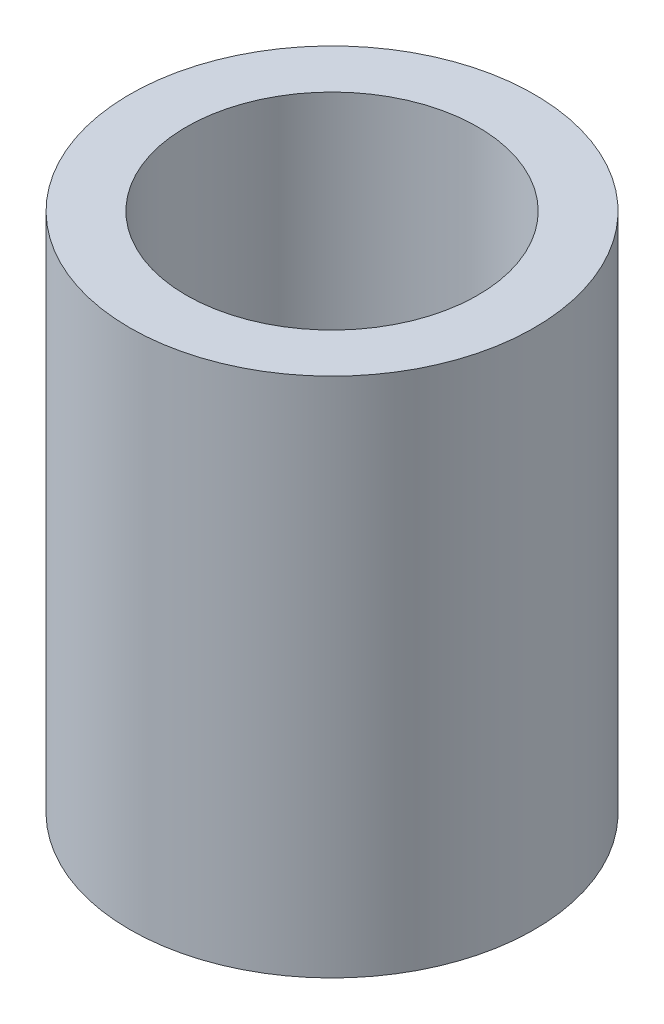
SolidWorks part; units mm, degrees
ref_plane "Front Plane" through (0, 0, 0) normal (0, 0, 1) x (1, 0, 0)
ref_plane "Top Plane" through (0, 0, 0) normal (0, 1, 0) x (1, 0, 0)
ref_plane "Right Plane" through (0, 0, 0) normal (1, 0, 0) x (0, 0, -1)
sketch "Sketch1" plane through (0, 0, 0) normal (0, 1, 0) x (1, 0, 0)
  circle A0 centre (0, 0) radius 20
  dimension "SLEEVE_OD" = 40
extrude "Boss-Extrude1" add sketch "Sketch1" along normal blind 51.5399
sketch "Sketch2" plane through (0, 0, 0) normal (0, 1, 0) x (1, 0, 0)
  circle A0 centre (0, 0) radius 14.4164
  dimension "BORE_D" = 28.8329
extrude "Cut-Extrude1" cut sketch "Sketch2" along normal through all
chamfer "Chamfer1" distance 3.5672 angle 43.793 rebuild error yes
